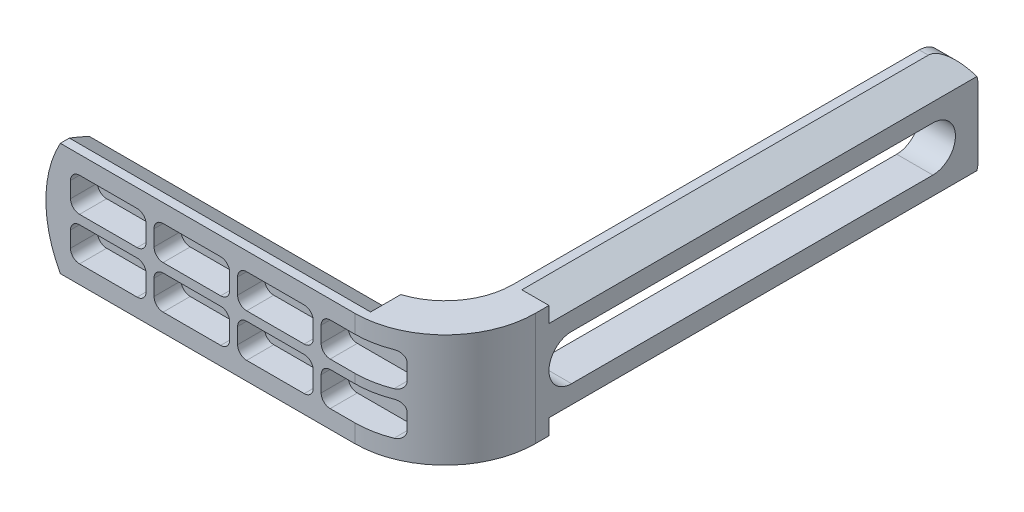
SolidWorks part; units mm, degrees
material "Сплав 2024"
ref_plane "Спереди" through (0, 0, 0) normal (0, 0, 1) x (1, 0, 0)
ref_plane "Сверху" through (0, 0, 0) normal (0, 1, 0) x (1, 0, 0)
ref_plane "Справа" through (0, 0, 0) normal (1, 0, 0) x (0, 0, -1)
sketch "Эскиз1" plane through (0, 0, 0) normal (0, 0, 1) x (1, 0, 0)
  line L1 (0, 0) -> (88.5, 0)
  line L2 (0, 0) -> (0, 25)
  line L3 (0, 25) -> (88.5, 25)
  line L4 (88.5, 0) -> (88.5, 25)
  dimension "D1" = 25
  dimension "D2" = 88.5
extrude "Бобышка-Вытянуть1" add sketch "Эскиз1" along normal blind 8
sketch "Эскиз4" plane through (0, 0, 0) normal (-1, 0, 0) x (0, 0, 1)
  line L0 (6, 0) -> (0, 3.4641)
  line L4 (0, 3.4641) -> (0, 0)
  line L5 (0, 0) -> (6, 0)
  line L6 (0, 12.5) -> (4.1286, 12.5) construction
  line L8 (0, 25) -> (6, 25)
  line L9 (0, 21.5359) -> (0, 25)
  line L11 (6, 25) -> (0, 21.5359)
  line L13 (0, 25) -> (0, 0) construction
  line L14 (8, 0) -> (0, 0) construction
  dimension "D1" = 2
  dimension "D2" = 30
extrude "Вырез-Вытянуть2" cut sketch "Эскиз4" against normal blind 70
sketch "Эскиз9" plane through (0, 0, 8) normal (0, 0, 1) x (1, 0, 0)
  line L0 (0, 12.5) -> (82.9468, 12.5) construction
  line L1 (0, 25) -> (0, 0) construction
  line L3 (5.5532, 13.5) -> (22.3032, 13.5)
  line L4 (5.5532, 13.5) -> (5.5532, 21)
  line L5 (5.5532, 21) -> (22.3032, 21)
  line L6 (22.3032, 13.5) -> (22.3032, 21)
  dimension "D1" = 7.5
  dimension "D2" = 1
  dimension "D3" = 16.75
  dimension "D4" = 5.5532
extrude "Вырез-Вытянуть3" cut sketch "Эскиз9" against normal offset from surface (6 mm away) 2 up to face at (57.125, 12.5, 0)
fillet "Скругление4" radius 2 4 edges at (5.5532, 13.5, 5) (22.3032, 13.5, 5) (22.3032, 21, 5) (5.5532, 21, 5)
pattern_linear "Линейный массив1" count 4 spacing 18.5 along (1, 0, 0) count 2 spacing 9.5 along (0, -1, 0) of "Скругление4", "Вырез-Вытянуть3"
sketch "Эскиз10" plane through (0, 0, 0) normal (0, 0, -1) x (-1, 0, 0)
  line L0 (-70, 0) -> (-88.5, 0) construction
  line L1 (-88.5, 25) -> (-80.5, 25)
  line L2 (-88.5, 25) -> (-88.5, 0)
  line L3 (-88.5, 0) -> (-80.5, 0)
  line L4 (-80.5, 25) -> (-80.5, 0)
  dimension "D1" = 8
extrude "Бобышка-Вытянуть2" add sketch "Эскиз10" along normal blind 110
fillet "Скругление5" radius 20 1 edges at (88.5, 12.5, 8)
fillet "Скругление6" radius 15 1 edges
fillet "Скругление7" radius 5 2 edges at (84.5, 0, -110) (84.5, 25, -110)
sketch "Эскиз11" plane through (0, 0, -110) normal (0, 0, -1) x (-1, 0, 0)
  line L0 (-82.5, 25) -> (-88.5, 25)
  line L2 (-88.5, 25) -> (-88.5, 21.5359)
  line L3 (-88.5, 20) -> (-88.5, 5) construction
  line L4 (-88.5, 21.5359) -> (-82.5, 25)
  line L5 (-80.5, 0) -> (-80.5, 25) construction
  line L6 (-80.5, 12.5) -> (-82.7763, 12.5) construction
  line L7 (-80.5, 5) -> (-80.5, 20) construction
  line L8 (-88.5, 3.4641) -> (-82.5, 0)
  line L9 (-88.5, 0) -> (-88.5, 3.4641)
  line L10 (-82.5, 0) -> (-88.5, 0)
  line L11 (-88.5, 25) -> (-88.5, 20) construction
  dimension "D1" = 2
  dimension "D2" = 30
extrude "Вырез-Вытянуть4" cut sketch "Эскиз11" against normal blind 95
sketch "Эскиз12" plane through (88.5, 0, 0) normal (1, 0, 0) x (0, 0, -1)
  line L0 (110, 12.5) -> (7.3499, 12.5) construction
  line L1 (110, 20) -> (110, 5) construction
  line L2 (20, 12.5) -> (100, 12.5) construction
  line L3 (20, 17.5) -> (100, 17.5)
  line L4 (20, 7.5) -> (100, 7.5)
  arc A0 (20, 17.5) -> (20, 7.5) centre (20, 12.5) ccw
  arc A1 (100, 7.5) -> (100, 17.5) centre (100, 12.5) ccw
  point P6 (60, 12.5)
  dimension "D1" = 10
  dimension "D2" = 80
  dimension "D3" = 10
extrude "Вырез-Вытянуть5" cut sketch "Эскиз12" against normal up to next
sketch "Эскиз13" plane through (0, 0, 0) normal (0, 0, -1) x (-1, 0, 0)
  line L0 (0, 12.5) -> (-5.3037, 12.5) construction
  line L1 (0, 21.5359) -> (0, 3.4641) construction
  line L2 (-3.302, 25) -> (0, 25)
  line L4 (0, 25) -> (0, 0)
  line L5 (0, 0) -> (-3.302, 0)
  line L6 (0, 0) -> (-88.5, 0) construction
  line L7 (-70, 25) -> (0, 25) construction
  arc A0 (-3.302, 0) -> (-3.302, 25) centre (-26.1, 12.5) ccw
  dimension "D1" = 52
  dimension "D2" = 26.1
extrude "Вырез-Вытянуть7" cut sketch "Эскиз13" against normal up to next
